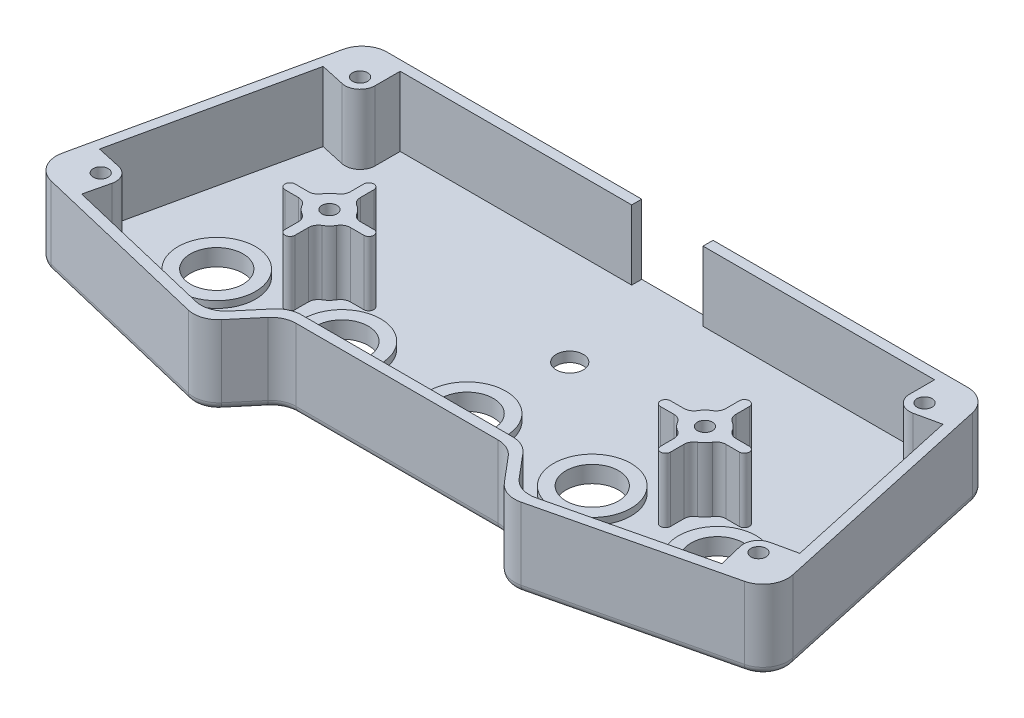
SolidWorks part; units mm, degrees
ref_plane "Front Plane" through (0, 0, 0) normal (0, 0, 1) x (1, 0, 0)
ref_plane "Top Plane" through (0, 0, 0) normal (0, 1, 0) x (1, 0, 0)
ref_plane "Right Plane" through (0, 0, 0) normal (1, 0, 0) x (0, 0, -1)
sketch "Sketch10" plane through (0, 0, 0) normal (0, 1, 0) x (1, 0, 0)
  line L0 (62, 32) -> (-62, 32)
  line L1 (-62, 32) -> (-74, -22.6992)
  line L2 (-74, -22.6992) -> (-30.236, -33.1736)
  line L3 (-30.236, -33.1736) -> (-22.5, -24)
  line L4 (-22.5, -24) -> (22.5, -24)
  line L5 (22.5, -24) -> (30.236, -33.1736)
  line L6 (30.236, -33.1736) -> (74, -22.6992)
  line L7 (74, -22.6992) -> (62, 32)
  line L8 (-50, -10) -> (-25, -10) construction
  line L9 (-25, -10) -> (0, -10) construction
  line L10 (0, -10) -> (25, -10) construction
  line L11 (25, -10) -> (50, -10) construction
  line L12 (-27, 0) -> (27, 0) construction
  line L13 (0, 0) -> (0, 32) construction
  line L14 (0, 0) -> (0, -24) construction
  line L15 (74, -22.6992) -> (22.5, -24) construction
  line L16 (-22.5, -24) -> (-74, -22.6992) construction
  circle A0 centre (50, -10) radius 5.25
  circle A2 centre (0, -10) radius 5.25
  circle A3 centre (25, -10) radius 5.25
  circle A5 centre (-50, -10) radius 5.25
  circle A6 centre (-25, -10) radius 5.25
  point P12 (-20, -10)
  dimension "D1" = 10.5
  dimension "D2" = 25
  dimension "D3" = 56
  dimension "D4" = 124
  dimension "D5" = 10
  dimension "D6" = 148
  dimension "D7" = 56
  dimension "D8" = 45
  dimension "D9" = 32
  dimension "D10" = 45
  dimension "D11" = 12
extrude "Boss-Extrude5" add sketch "Sketch10" along normal blind 2 separate body
sketch "Sketch11" plane through (0, 2, 0) normal (0, 1, 0) x (1, 0, 0)
  line L0 (-74, -22.6992) -> (-62, 32)
  line L1 (-62, 32) -> (62, 32)
  line L2 (62, 32) -> (74, -22.6992)
  line L3 (74, -22.6992) -> (30.236, -33.1736)
  line L4 (30.236, -33.1736) -> (22.5, -24)
  line L5 (22.5, -24) -> (-22.5, -24)
  line L6 (-22.5, -24) -> (-30.236, -33.1736)
  line L7 (-30.236, -33.1736) -> (-74, -22.6992)
  line L8 (-30.9699, -30.9414) -> (-71.6259, -21.2109)
  line L9 (-71.6259, -21.2109) -> (-60.3912, 30)
  line L10 (-60.3912, 30) -> (60.3912, 30)
  line L11 (60.3912, 30) -> (71.6259, -21.2109)
  line L12 (71.6259, -21.2109) -> (30.9699, -30.9414)
  line L13 (30.9699, -30.9414) -> (23.4296, -22)
  line L14 (23.4296, -22) -> (-23.4296, -22)
  line L15 (-23.4296, -22) -> (-30.9699, -30.9414)
  dimension "D1" = 2
extrude "Boss-Extrude7" add sketch "Sketch11" along direction (0, -1, 0) on the side of the normal offset from surface (13.875 mm away) 15.875 up to face at (-50, 0, 15.25)
fillet "Fillet4" radius 5 16 edges at (62, 7.9375, -32) (74, 7.9375, 22.6992) (30.236, 7.9375, 33.1736) (22.5, 7.9375, 24) (-22.5, 7.9375, 24) (-30.236, 7.9375, 33.1736) (-62, 7.9375, -32) (-74, 7.9375, 22.6992) (71.6259, 8.9375, 21.2109) (60.3912, 8.9375, -30) (30.9699, 8.9375, 30.9414) (23.4296, 8.9375, 22) (-23.4296, 8.9375, 22) (-30.9699, 8.9375, 30.9414) (-71.6259, 8.9375, 21.2109) (-60.3912, 8.9375, -30)
fillet "Fillet5" radius 1.5 16 edges at (30.509, 0, 32.3431) (26.1233, 0, 28.2966) (22.2835, 0, 24.4659) (0, 0, 24) (-22.2835, 0, 24.4659) (-26.1233, 0, 28.2966) (-30.509, 0, 32.3431) (-51.2316, 0, 28.1485) (-72.3012, 0, 21.6342) (-67.9053, 0, -5.0822) (-61.1119, 0, -30.896) (0, 0, -32) (61.1119, 0, -30.896) (67.9053, 0, -5.0822) (72.3012, 0, 21.6342) (51.2316, 0, 28.1485)
sketch "Sketch12" plane through (0, 2, 0) normal (0, 1, 0) x (1, 0, 0)
  line L0 (-61.8959, 23.1411) -> (-57.0121, 22.0697)
  line L1 (-61.2531, 26.0714) -> (-70.5746, -16.4188) construction
  line L2 (-53.3692, 25) -> (-53.3692, 30)
  line L3 (56.3692, 30) -> (-56.3692, 30) construction
  line L4 (-53.3692, 30) -> (-56.3692, 30)
  line L5 (-61.2531, 26.0714) -> (-61.8959, 23.1411)
  line L6 (-70.5746, -16.4188) -> (-69.9318, -13.4885)
  line L7 (-69.9318, -13.4885) -> (-65.0479, -14.5599)
  line L8 (-62.7732, -18.1885) -> (-63.937, -23.0512)
  line L9 (-66.8546, -22.3529) -> (-33.9684, -30.2238) construction
  line L10 (-63.937, -23.0512) -> (-66.8546, -22.3529)
  line L11 (0, 0) -> (0, 17.9434) construction
  line L12 (63.937, -23.0512) -> (66.8546, -22.3529)
  line L13 (62.7732, -18.1885) -> (63.937, -23.0512)
  line L14 (69.9318, -13.4885) -> (65.0479, -14.5599)
  line L15 (70.5746, -16.4188) -> (69.9318, -13.4885)
  line L16 (61.2531, 26.0714) -> (61.8959, 23.1411)
  line L17 (53.3692, 30) -> (56.3692, 30)
  line L18 (53.3692, 25) -> (53.3692, 30)
  line L19 (61.8959, 23.1411) -> (57.0121, 22.0697)
  arc A0 (-57.0121, 22.0697) -> (-53.3692, 25) centre (-56.3692, 25) ccw
  arc A1 (-56.3692, 30) -> (-61.2531, 26.0714) centre (-56.3692, 25) ccw
  arc A2 (-65.0479, -14.5599) -> (-62.7732, -18.1885) centre (-65.6908, -17.4902) cw
  arc A3 (-66.8546, -22.3529) -> (-70.5746, -16.4188) centre (-65.6908, -17.4902) cw
  circle A4 centre (-56.3692, 25) radius 1.5
  circle A5 centre (-65.6908, -17.4902) radius 1.5
  circle A6 centre (65.6908, -17.4902) radius 1.5
  circle A7 centre (56.3692, 25) radius 1.5
  arc A8 (66.8546, -22.3529) -> (70.5746, -16.4188) centre (65.6908, -17.4902) ccw
  arc A9 (65.0479, -14.5599) -> (62.7732, -18.1885) centre (65.6908, -17.4902) ccw
  arc A10 (56.3692, 30) -> (61.2531, 26.0714) centre (56.3692, 25) cw
  arc A11 (57.0121, 22.0697) -> (53.3692, 25) centre (56.3692, 25) cw
  dimension "D1" = 3
  dimension "D2" = 1.5
extrude "Boss-Extrude8" add sketch "Sketch12" along normal up to surface (13.875 mm away) up to face at (0, 15.875, 10.9337)
sketch "Sketch14" plane through (0, 0, -30) normal (0, 0, 1) x (1, 0, 0)
  line L0 (-53.3692, 15.875) -> (53.3692, 15.875) construction
  line L5 (0, 0) -> (0, 15.875) construction
  line L10 (-6.625, 15.03) -> (-6.625, 2.5) construction
  line L11 (-7.125, 15.875) -> (7.125, 15.875)
  line L12 (-7.125, 15.875) -> (-7.125, 2)
  line L13 (-7.125, 2) -> (7.125, 2)
  line L14 (7.125, 15.875) -> (7.125, 2)
  line L15 (53.3692, 2) -> (-53.3692, 2) construction
  dimension "D1" = 0.5
extrude "Cut-Extrude2" cut sketch "Sketch14" against normal through all
sketch "Sketch15" plane through (0, 0, 0) normal (0, -1, 0) x (1, 0, 0)
  line L0 (0, -10.5) -> (0, -30.5) construction
  line L1 (-57.978, -30.5) -> (57.978, -30.5) construction
  circle A0 centre (0, -10.5) radius 2.7
  dimension "D2" = 5.4
  dimension "D1" = 20
extrude "Cut-Extrude3" cut sketch "Sketch15" against normal through all contours A0
sketch "Sketch16" plane through (0, 2, 0) normal (0, 1, 0) x (1, 0, 0)
  circle A0 centre (25, -10) radius 7.75
  circle A1 centre (25, -10) radius 5.25
  circle A2 centre (0, -10) radius 7.75
  circle A3 centre (0, -10) radius 5.25
  circle A4 centre (-50, -10) radius 5.25
  circle A5 centre (-50, -10) radius 7.75
  circle A6 centre (-25, -10) radius 5.25
  circle A7 centre (-25, -10) radius 7.75
  circle A9 centre (-50, -10) radius 5.25 construction
  circle A10 centre (-25, -10) radius 5.25 construction
  circle A12 centre (25, -10) radius 5.25 construction
  circle A13 centre (0, -10) radius 5.25 construction
  circle A14 centre (50, -10) radius 7.75
  circle A15 centre (50, -10) radius 5.25
  circle A16 centre (50, -10) radius 5.25 construction
  point P15 (0, 0)
  point P21 (0, -8)
  point P28 (39.7122, -8)
  dimension "D1" = 2.5
extrude "Boss-Extrude9" add sketch "Sketch16" along normal blind 1.35
sketch "Sketch17" plane through (0, 2, 0) normal (0, 1, 0) x (1, 0, 0)
  line L0 (-38.5, 3.873) -> (-38.5, 7.873)
  line L3 (-36.5, 7.873) -> (-36.5, 3.873)
  line L4 (-33.627, 1) -> (-29.627, 1)
  line L5 (-29.627, -1) -> (-33.627, -1)
  line L8 (-41.373, -1) -> (-45.373, -1)
  line L9 (-45.373, 1) -> (-41.373, 1)
  line L10 (-45.373, 0) -> (-37.5, 0) construction
  line L11 (-37.5, 0) -> (-29.627, 0) construction
  line L12 (-37.5, -1.5) -> (-37.5, 0) construction
  line L13 (-37.5, 7.873) -> (-37.5, 0) construction
  line L14 (-38.5, -3.873) -> (-38.5, -7.873)
  line L15 (-37.5, 0) -> (0, 0) construction
  line L16 (-36.5, -7.873) -> (-36.5, -3.873)
  line L17 (-37.5, -7.873) -> (-37.5, 0) construction
  arc A0 (-38.5, 3.873) -> (-41.373, 1) centre (-37.5, 0) ccw
  arc A3 (-38.5, 7.873) -> (-36.5, 7.873) centre (-37.5, 7.873) cw
  arc A4 (-29.627, 1) -> (-29.627, -1) centre (-29.627, 0) cw
  arc A6 (-45.373, -1) -> (-45.373, 1) centre (-45.373, 0) cw
  arc A7 (-33.627, 1) -> (-36.5, 3.873) centre (-37.5, 0) ccw
  arc A8 (-41.373, -1) -> (-38.5, -3.873) centre (-37.5, 0) ccw
  circle A10 centre (-37.5, 0) radius 1.5
  arc A11 (-38.5, -7.873) -> (-36.5, -7.873) centre (-37.5, -7.873) ccw
  arc A12 (-36.5, -3.873) -> (-33.627, -1) centre (-37.5, 0) ccw
  dimension "D1" = 37.5
  dimension "D4" = 8
  dimension "D5" = 3
  dimension "D2" = 2
  dimension "D3" = 4
extrude "PCB Mount Posts" add sketch "Sketch17" along normal offset from surface (12.875 mm away) 1 up to face at (0, 15.875, 4.8751)
fillet "Fillet6" radius 2 8 edges at (-41.373, 8.4375, -1) (-38.5, 8.4375, -3.873) (-36.5, 8.4375, -3.873) (-33.627, 8.4375, -1) (-33.627, 8.4375, 1) (-36.5, 8.4375, 3.873) (-38.5, 8.4375, 3.873) (-41.373, 8.4375, 1)
mirror "Mirror1" about plane through (0, 0, 0) normal (1, 0, 0) of "Fillet6", "Boss-Extrude9", "PCB Mount Posts"
sketch "Sketch18" plane through (0, 0, 0) normal (0, -1, 0) x (1, 0, 0)
  line L0 (61.9419, 3.1649) -> (38.0581, 3.1649) construction
  line L1 (50, 10) -> (50, 3.1649) construction
  circle A0 centre (50, 10) radius 5.25 construction
  text T0 "PENALTY" font "Century Gothic" height 4
  point P4 (0, 0)
  point P7 (61.9419, 3.1649)
sketch "Sketch19" plane through (0, 0, 0) normal (0, -1, 0) x (1, 0, 0)
  line L0 (37.3409, -3.8991) -> (12.6591, -3.8991) construction
  line L1 (25, 10) -> (25, -3.8991) construction
  circle A1 centre (25, 10) radius 5.25 construction
  text T0 "START/\r\nRESUME" font "Century Gothic" height 4
  point P4 (-13.1006, 18.2488)
  point P5 (25.7285, 10.1547)
  point P7 (48.8413, 21.4137)
  point P10 (37.3409, 3.1626)
extrude "Cut-Extrude4" cut sketch "Sketch18" against normal blind 0.5
sketch "Sketch20" plane through (0, 0, 0) normal (0, -1, 0) x (1, 0, 0)
  line L0 (7.5418, 0.7099) -> (-7.5418, 0.7099) construction
  line L1 (0, 10) -> (0, 0.7099) construction
  circle A0 centre (0, 10) radius 5.25 construction
  text T0 "RESET\r\n" font "Century Gothic" height 4
  point P4 (-32.6601, 36.0941)
  point P5 (6.169, 28)
  point P6 (0.6413, 10.039)
  point P7 (29.2818, 39.2591)
  point P10 (17.7814, 21.0079)
sketch "Sketch21" plane through (0, 0, 0) normal (0, -1, 0) x (1, 0, 0)
  line L0 (-17.4582, -3.6884) -> (-32.5418, -3.6884) construction
  line L1 (-25, 10) -> (-25, -3.6884) construction
  circle A1 centre (-25, 10) radius 5.25 construction
  text T0 "PAUSE" font "Century Gothic" height 4
  point P4 (-61.0579, 31.6957)
  point P5 (-22.2288, 23.6016)
  point P6 (-27.7565, 5.6406)
  point P7 (0.884, 34.8607)
  point P9 (0, 0)
  point P10 (-10.6164, 16.6095)
sketch "Sketch22" plane through (0, 0, 0) normal (0, -1, 0) x (1, 0, 0)
  line L0 (-37.6344, 1.385) -> (-62.3656, 1.385) construction
  line L1 (-50, 10) -> (-50, 1.385) construction
  circle A1 centre (-50, 10) radius 5.25 construction
  text T0 "PENALTY" font "Century Gothic" height 4
  point P4 (-88.5312, 16.0931)
  point P5 (-49.9761, 10.5916)
  point P7 (-26.5893, 19.258)
  point P10 (-37.6344, 1.385)
